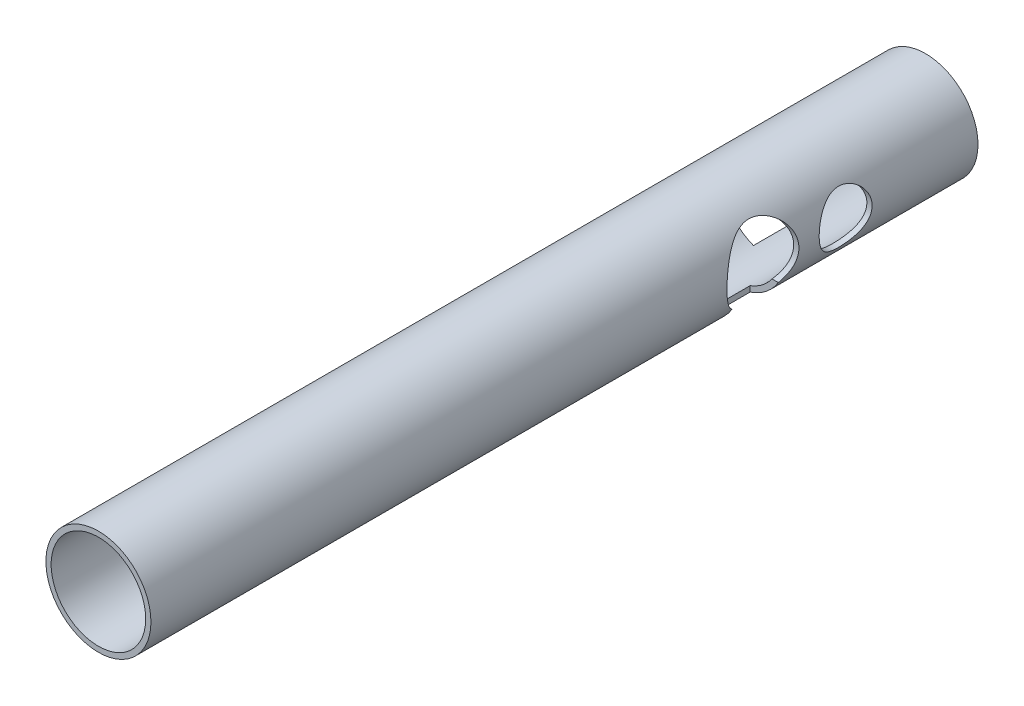
SolidWorks part; units mm, degrees
ref_plane "Front Plane" through (0, 0, 0) normal (0, 0, 1) x (1, 0, 0)
ref_plane "Top Plane" through (0, 0, 0) normal (0, 1, 0) x (1, 0, 0)
ref_plane "Right Plane" through (0, 0, 0) normal (1, 0, 0) x (0, 0, -1)
sketch "Sketch1" plane through (0, 0, 0) normal (0, 0, 1) x (1, 0, 0)
  circle A0 centre (0, 0) radius 31.75
  circle A1 centre (0, 0) radius 28.575
  dimension "D1" = 63.5
  dimension "D2" = 57.15
extrude "Boss-Extrude1" add sketch "Sketch1" along normal blind 250 and the other way blind 250 contours A1 | A0 region at (0, 0, 0)
sketch "Sketch2" plane through (0, 0, 0) normal (1, 0, 0) x (0, 0, -1)
  circle A0 centre (170, 0) radius 21.75
  circle A1 centre (120, 0) radius 16
  dimension "D1" = 32
  dimension "D2" = 43.5
  dimension "D3" = 170
  dimension "D4" = 120
extrude "Cut-Extrude1" cut sketch "Sketch2" against normal through all
sketch "Sketch3" plane through (0, 0, 0) normal (1, 0, 0) x (0, 0, -1)
  circle A0 centre (170, 0) radius 16
  circle A1 centre (120, 0) radius 21.75
  dimension "D1" = 43.5
  dimension "D2" = 32
  dimension "D3" = 120
  dimension "D4" = 170
extrude "Cut-Extrude2" cut sketch "Sketch3" along normal through all
sketch "Sketch4" plane through (0, 0, 0) normal (1, 0, 0) x (0, 0, -1)
  line L1 (106, -10.75) -> (134, -10.75)
  line L2 (106, -10.75) -> (106, -32.75)
  line L3 (106, -32.75) -> (134, -32.75)
  line L4 (134, -10.75) -> (134, -32.75)
  line L5 (106, -10.75) -> (134, -32.75) construction
  line L6 (106, -32.75) -> (134, -10.75) construction
  circle A0 centre (120, 0) radius 21.75 construction
  circle A1 centre (120, 0) radius 21.75 construction
  point P0 (120, -21.75)
  dimension "D1" = 28
  dimension "D2" = 22
  dimension "D3" = 120
extrude "Cut-Extrude3" cut sketch "Sketch4" along normal blind 20 from offset 10
sketch "Sketch5" plane through (0, 0, 0) normal (1, 0, 0) x (0, 0, -1)
  line L1 (184, -10.75) -> (156, -10.75)
  line L2 (184, -10.75) -> (184, -32.75)
  line L3 (184, -32.75) -> (156, -32.75)
  line L4 (156, -10.75) -> (156, -32.75)
  line L5 (184, -10.75) -> (156, -32.75) construction
  line L6 (184, -32.75) -> (156, -10.75) construction
  circle A0 centre (170, 0) radius 21.75 construction
  circle A1 centre (170, 0) radius 21.75 construction
  point P0 (170, -21.75)
  dimension "D1" = 28
  dimension "D2" = 22
  dimension "D3" = 170
extrude "Cut-Extrude4" cut sketch "Sketch5" against normal blind 20 from offset 10 offset against normal yes
